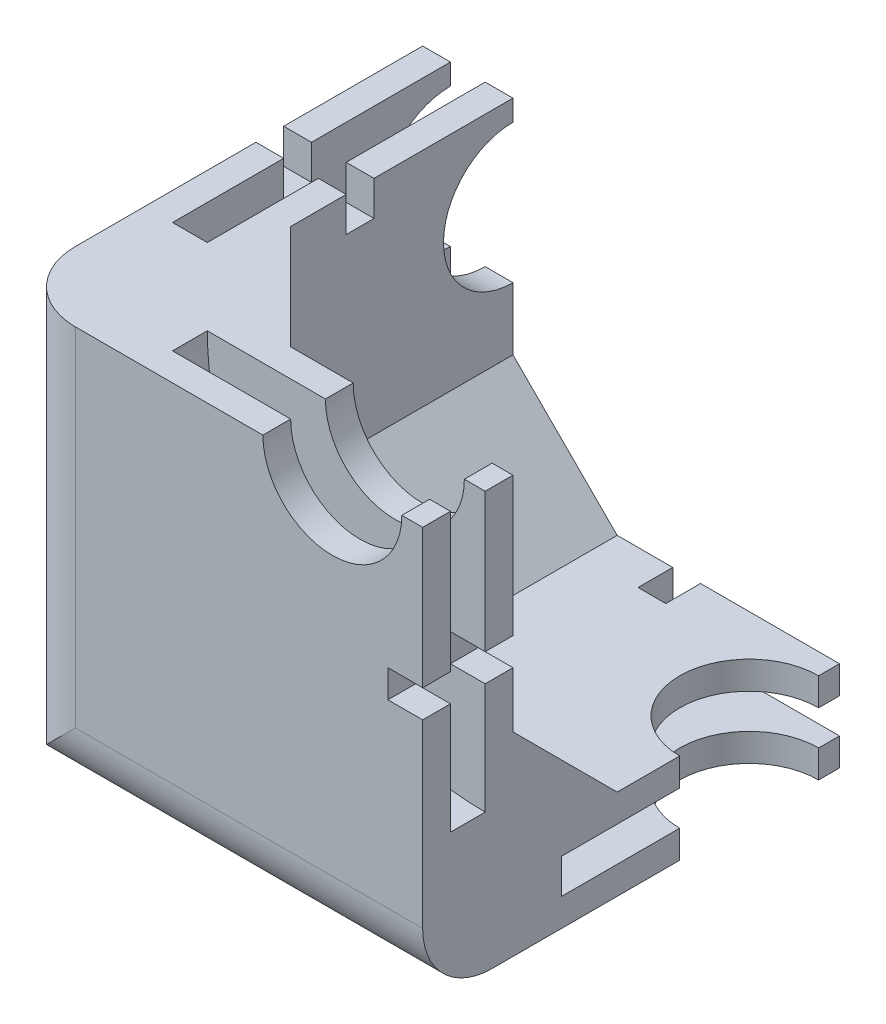
SolidWorks part; units mm, degrees
ref_plane "前视基准面" through (0, 0, 0) normal (0, 0, 1) x (1, 0, 0)
ref_plane "上视基准面" through (0, 0, 0) normal (0, 1, 0) x (1, 0, 0)
ref_plane "右视基准面" through (0, 0, 0) normal (1, 0, 0) x (0, 0, -1)
other "Configuration Table"
sketch "草图1" plane through (0, 0, 0) normal (0, 1, 0) x (1, 0, 0)
  line L1 (-30, 30) -> (30, 30)
  line L2 (-30, 30) -> (-30, -30)
  line L3 (-30, -30) -> (30, -30)
  line L4 (30, 30) -> (30, -30)
  line L5 (-30, 30) -> (30, -30) construction
  line L6 (-30, -30) -> (30, 30) construction
  point P0 (0, 0)
  dimension "D1" = 60
  dimension "D2" = 60
extrude "凸台-拉伸2" add sketch "草图1" along normal mid plane 60
fillet "圆角4" radius 10 2 edges at (-30, -30, 0) (0, -30, 30) tangent propagation no
fillet "圆角5" radius 10 1 edges at (-30, 5, 30) tangent propagation no
sketch "草图5" plane through (0, 30, 0) normal (0, 1, 0) x (1, 0, 0)
  line L0 (30, -30) -> (30, 30) construction
  line L1 (30, 30) -> (-17, 30)
  line L2 (30, 30) -> (30, -17)
  line L3 (30, -17) -> (-17, -17)
  line L4 (-17, 30) -> (-17, -17)
  line L5 (30, 30) -> (-30, 30) construction
  line L6 (-20, -30) -> (30, -30) construction
  line L7 (-30, 30) -> (-30, -20) construction
  dimension "D1" = 0
  dimension "D2" = 13
  dimension "D3" = 13
extrude "切除-拉伸4" cut sketch "草图5" against normal offset from surface (47 mm away) 13 up to face at (5, -30, -5)
chamfer "倒角3" distance 15 angle 45 2 edges at (6.5, -17, 17) (-17, -17, -6.5)
chamfer "倒角4" distance 15 angle 45 1 edges at (-17, 14, 17) tangent propagation no
sketch "草图6" plane through (0, 0, 30) normal (0, 0, 1) x (1, 0, 0)
  circle A0 centre (30, 30) radius 40
  dimension "D1" = 80
extrude "切除-拉伸5" cut sketch "草图6" against normal blind 5 from offset 4 offset against normal yes
sketch "草图7" plane through (0, 0, 30) normal (0, 0, 1) x (1, 0, 0)
  line L0 (-20, 30) -> (30, 30) construction
  line L1 (30, 30) -> (30, -20) construction
  line L3 (30, 10) -> (25, 10)
  line L4 (30, 10) -> (30, 6)
  line L5 (30, 6) -> (25, 6)
  line L6 (25, 10) -> (25, 6)
  circle A0 centre (17, 30) radius 10
  dimension "D2" = 20
  dimension "D1" = 13
  dimension "D3" = 4
  dimension "D4" = 5
  dimension "D5" = 20
extrude "切除-拉伸6" cut sketch "草图7" against normal blind 13
ref_axis "基准轴2" through (-9.5, -9.5, 9.5) along (0.5774, 0.5774, -0.5774)
pattern_circular "阵列(圆周)5" count 3 over 360 about axis through (-9.5, -9.5, 9.5) along (0.5774, 0.5774, -0.5774) of "切除-拉伸5", "切除-拉伸6"
